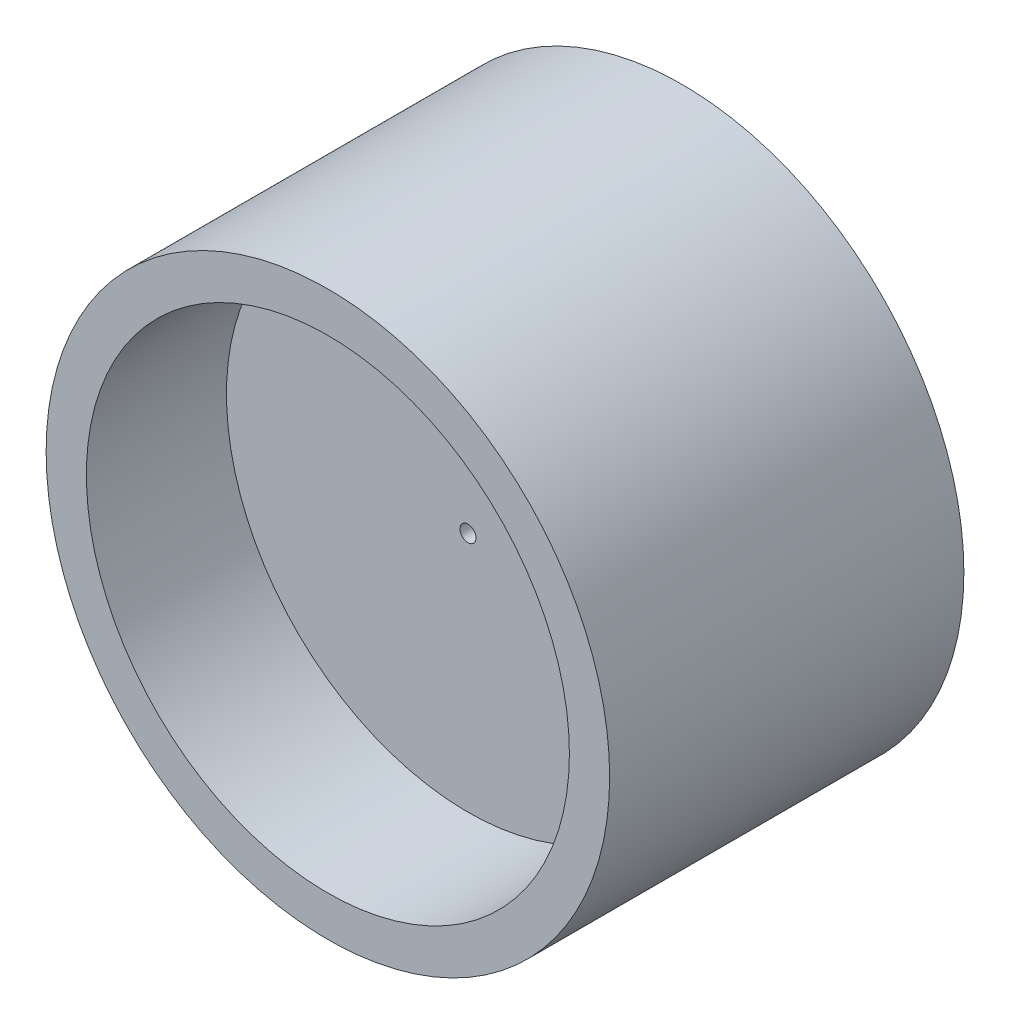
SolidWorks part; units mm, degrees
ref_plane "Front Plane" through (0, 0, 0) normal (0, 0, 1) x (1, 0, 0)
ref_plane "Top Plane" through (0, 0, 0) normal (0, 1, 0) x (1, 0, 0)
ref_plane "Right Plane" through (0, 0, 0) normal (1, 0, 0) x (0, 0, -1)
sketch "Sketch1" plane through (0, 0, 0) normal (0, 0, 1) x (1, 0, 0)
  circle A0 centre (0, 0) radius 44.45
  dimension "D1" = 88.9
extrude "Boss-Extrude1" add sketch "Sketch1" along normal blind 55.88
sketch "Sketch2" plane through (0, 0, 55.88) normal (0, 0, 1) x (1, 0, 0)
  circle A0 centre (0, 0) radius 38.1
  dimension "D1" = 76.2
extrude "Cut-Extrude1" cut sketch "Sketch2" against normal blind 22.098
sketch "Sketch3" plane through (0, 0, 0) normal (0, 0, -1) x (-1, 0, 0)
  circle A0 centre (0, 0) radius 38.1
  dimension "D1" = 76.2
extrude "Cut-Extrude2" cut sketch "Sketch3" against normal blind 28.575
sketch "Sketch4" plane through (0, 0, 33.782) normal (0, 0, 1) x (1, 0, 0)
  circle A0 centre (0, 0) radius 1.27
  dimension "D1" = 2.54
extrude "Cut-Extrude3" cut sketch "Sketch4" against normal through all
